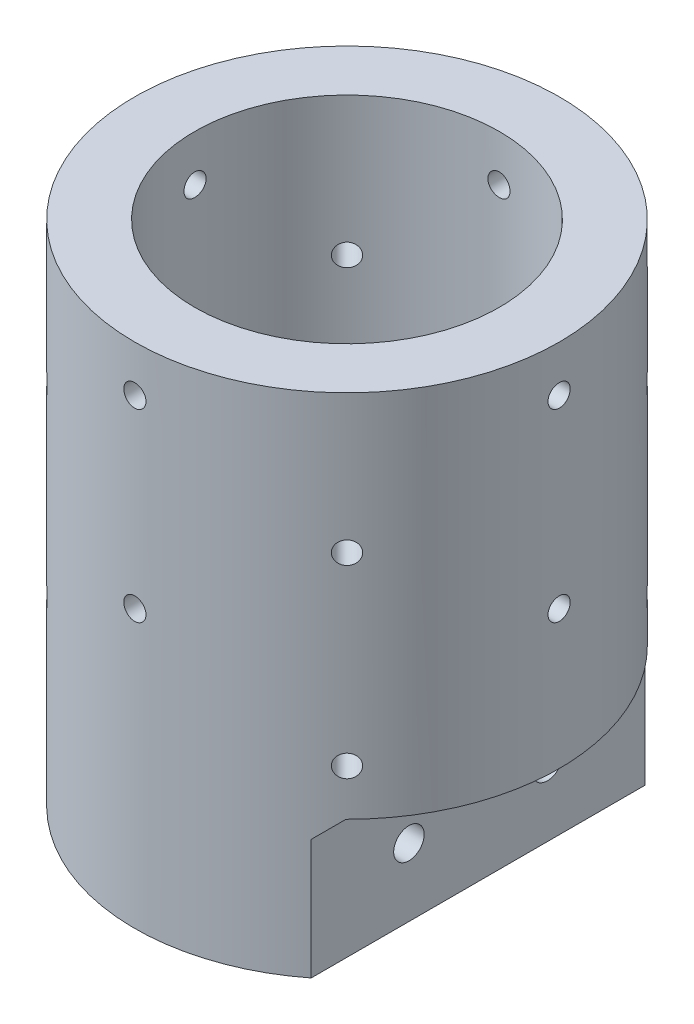
SolidWorks part; units mm, degrees
ref_plane "Спереди" through (0, 0, 0) normal (0, 0, 1) x (1, 0, 0)
ref_plane "Сверху" through (0, 0, 0) normal (0, 1, 0) x (1, 0, 0)
ref_plane "Справа" through (0, 0, 0) normal (1, 0, 0) x (0, 0, -1)
sketch "Эскиз1" plane through (0, 0, 0) normal (0, 1, 0) x (1, 0, 0)
  circle A0 centre (0, 0) radius 23
  dimension "D1" = 46
extrude "Бобышка-Вытянуть1" add sketch "Эскиз1" along normal blind 5
sketch "Эскиз2" plane through (0, 5, 0) normal (0, 1, 0) x (1, 0, 0)
  circle A0 centre (0, 0) radius 23
  circle A1 centre (0, 0) radius 16.5
  circle A2 centre (0, 0) radius 23 construction
  dimension "D1" = 33
  dimension "D2" = 0
extrude "Бобышка-Вытянуть2" add sketch "Эскиз2" along normal blind 35
chamfer "Фаска8" distance 2 angle 45 1 edges at (0, 5, 16.5)
sketch "Эскиз3" plane through (0, 0, 0) normal (1, 0, 0) x (0, 0, -1)
  line L0 (-23, 20) -> (28.0263, 20) construction
  line L1 (-23, 40) -> (-23, 0) construction
  line L2 (16.5, 40) -> (-16.5, 40) construction
  circle A1 centre (0, 35) radius 1.2
  dimension "D1" = 2.4
  dimension "D2" = 5
extrude "Вырез-Вытянуть1" cut sketch "Эскиз3" against normal through all
ref_plane "Плоскость1" through (0, 0, 0) normal (0.7071, 0, 0.7071) x (0, -1, 0)
sketch "Эскиз4" plane through (0, 0, 0) normal (0.7071, 0, 0.7071) x (0, -1, 0)
  line L0 (-20, 23) -> (-20, -30.0625) construction
  line L1 (0, 23) -> (-40, 23) construction
  line L3 (0, -23) -> (0, 23) construction
  circle A1 centre (-5, 0) radius 1.2
  dimension "D1" = 5
  dimension "D2" = 2.4
extrude "Вырез-Вытянуть2" cut sketch "Эскиз4" against normal through all from offset 16.3 offset against normal yes
pattern_circular "Круговой массив1" count 4 over 360 about axis through (0, 5, 0) along (0, -1, 0) of "Вырез-Вытянуть2"
pattern_circular "Круговой массив2" count 4 over 360 about axis through (0, 5, 0) along (0, -1, 0) of "Вырез-Вытянуть1"
pattern_linear "Линейный массив3" count 2 spacing 20 along (0, 1, 0) of "Круговой массив1"
pattern_linear "Линейный массив4" count 2 spacing 20 along (0, -1, 0) of "Круговой массив2"
sketch "Эскиз12" plane through (0, 0, 0) normal (0, -1, 0) x (1, 0, 0)
  line L1 (14.207, 18.0876) -> (14.207, -18.0876)
  line L20 (0, 15) -> (-2.7835, 17.7835)
  line L21 (-2.7835, -17.7835) -> (0, -15)
  line L22 (0, -15) -> (0, 15)
  line L23 (0, 15) -> (-2.7835, 17.7835)
  line L24 (-2.7835, -17.7835) -> (0, -15)
  line L25 (0, -15) -> (0, 15)
  circle A6 centre (0, 0) radius 23 construction
  arc A7 (14.207, 18.0876) -> (14.207, -18.0876) centre (0, 0) ccw
  arc A13 (-2.7835, 17.7835) -> (-2.7835, -17.7835) centre (0, 0) ccw
  arc A14 (-2.7835, 17.7835) -> (-2.7835, -17.7835) centre (0, 0) ccw
  point P9 (0, 0)
  dimension "D1" = 0
extrude "Бобышка-Вытянуть3" add sketch "Эскиз12" along normal blind 15 contours L1 region at (13.6153, 0, 0)
sketch "Эскиз13" plane through (0, -15, 0) normal (0, -1, 0) x (1, 0, 0)
  line L14 (-2.6786, -18.1029) -> (0.3, -15.1243)
  line L15 (0.3, 15.1243) -> (-2.6786, 18.1029)
  line L16 (0.3, -15.1243) -> (0.3, 15.1243)
  line L17 (-2.6786, -18.1029) -> (0.3, -15.1243)
  line L18 (0.3, 15.1243) -> (-2.6786, 18.1029)
  line L19 (0.3, -15.1243) -> (0.3, 15.1243)
  arc A5 (-2.6786, 18.1029) -> (-2.6786, -18.1029) centre (0, 0) ccw
  arc A6 (-2.6786, 18.1029) -> (-2.6786, -18.1029) centre (0, 0) ccw
  dimension "D1" = 0.3
extrude "Вырез-Вытянуть10" cut sketch "Эскиз13" against normal up to surface (15 mm away) up to face at (18.6035, 0, 0)
chamfer "Фаска4" distance 2 angle 45 1 edges at (14.207, 0, 0)
chamfer "Фаска6" distance 2 angle 45 4 edges at (-1.1893, 0, -16.6136) (-18.3, 0, 0) (0.3, 0, 0) (-1.1893, 0, 16.6136)
chamfer "Фаска7" distance 2 angle 45 4 edges at (-1.1893, -15, -16.6136) (-18.3, -15, 0) (-1.1893, -15, 16.6136) (0.3, -15, 0)
extrude "Вырез-Вытянуть11" cut sketch "Эскиз14" against normal blind 33
sketch "Эскиз14" plane through (14.207, -656.2045, -24.0267) normal (1, 0, 0) x (0, 0.0202, -0.9998)
  line L2 (-10.8359, 654.256) -> (-11.0516, 643.5582) construction
  line L7 (-18.4422, 649.0583) -> (-10.9438, 648.9071) construction
  circle A0 centre (-18.4422, 649.0583) radius 1.65
  circle A1 centre (-3.4453, 648.7559) radius 1.65
